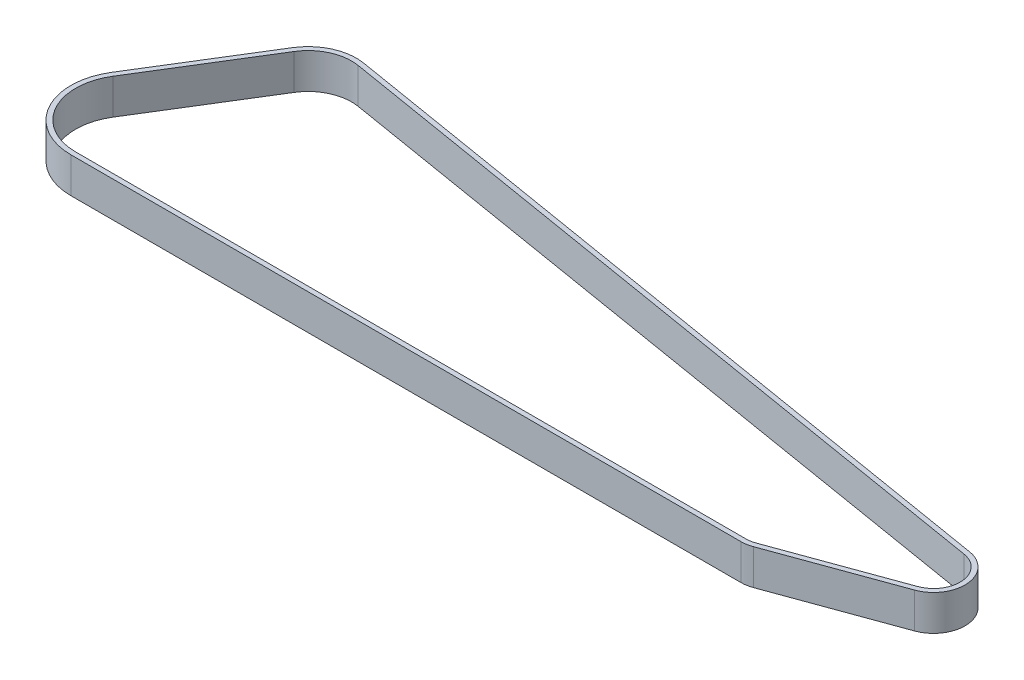
SolidWorks part; units mm, degrees
ref_plane "前视基准面" through (0, 0, 0) normal (0, 0, 1) x (1, 0, 0)
ref_plane "上视基准面" through (0, 0, 0) normal (0, 1, 0) x (1, 0, 0)
ref_plane "右视基准面" through (0, 0, 0) normal (1, 0, 0) x (0, 0, -1)
sketch "草图1" plane through (0, 0, 0) normal (0, 1, 0) x (1, 0, 0)
  line L1 (-17.5, -27.5) -> (17.5, -27.5)
  line L2 (-17.5, -27.5) -> (-17.5, 27.5)
  line L3 (-17.5, 27.5) -> (17.5, 27.5)
  line L4 (17.5, -27.5) -> (17.5, 27.5)
  line L5 (-17.5, -27.5) -> (17.5, 27.5) construction
  line L6 (-17.5, 27.5) -> (17.5, -27.5) construction
  point P0 (0, 0)
  dimension "D1" = 55
  dimension "D2" = 35
extrude "凸台-拉伸1" add sketch "草图1" along normal blind 1
sketch "草图2" plane through (0, 1, 0) normal (0, 1, 0) x (1, 0, 0)
  line L0 (-105.917, 0) -> (-62.25, 0) construction
  line L1 (106.75, 2.25) -> (121.75, 2.25)
  line L2 (-31.4474, 57.1013) -> (151.75, 26.6691)
  line L4 (124.0586, 2.6571) -> (154.0586, 13.5762)
  line L5 (-60.1618, 23.6059) -> (-42.6093, 52.0296)
  line L6 (121.75, 2.25) -> (121.75, 9) construction
  line L7 (121.75, -2.25) -> (121.75, -9) construction
  line L8 (-60.1618, -23.6059) -> (-42.6093, -52.0296)
  line L9 (124.0586, -2.6571) -> (154.0586, -13.5762)
  line L10 (121.75, -9) -> (128.5, -9)
  line L11 (-31.4474, -57.1013) -> (151.75, -26.6691)
  line L12 (106.75, -2.25) -> (121.75, -2.25)
  line L13 (-62.25, 16.25) -> (-62.25, -16.25)
  line L14 (106.75, 2.25) -> (106.75, -2.25)
  line L15 (106.75, 0) -> (124.0666, 0) construction
  arc A0 (-60.1618, 23.6059) -> (-62.25, 16.25) centre (-48.25, 16.25) ccw
  arc A1 (-31.4474, 57.1013) -> (-42.6093, 52.0296) centre (-33.25, 46.25) ccw
  arc A2 (121.75, 2.25) -> (124.0586, 2.6571) centre (121.75, 9) ccw
  arc A3 (154.0586, 13.5762) -> (151.75, 26.6691) centre (151.75, 19.9191) ccw
  arc A4 (154.0586, -13.5762) -> (151.75, -26.6691) centre (151.75, -19.9191) cw
  arc A5 (121.75, -2.25) -> (128.5, -9) centre (121.75, -9) cw
  arc A6 (-31.4474, -57.1013) -> (-42.6093, -52.0296) centre (-33.25, -46.25) cw
  arc A7 (-60.1618, -23.6059) -> (-62.25, -16.25) centre (-48.25, -16.25) cw
  line M10 (17.5, -27.5) -> (17.5, 27.5)
  line M11 (17.5, 27.5) -> (-17.5, 27.5)
  line M12 (-17.5, 27.5) -> (-17.5, -27.5)
  line M13 (-17.5, -27.5) -> (17.5, -27.5)
  dimension "D2" = 28
  dimension "D3" = 48.25
  dimension "D4" = 22
  dimension "D5" = 15
  dimension "D7" = 13.5
  dimension "D10" = 13.5
  dimension "D11" = 30
  dimension "D1" = 2.25
  dimension "D8" = 20
  dimension "D9" = 30
  dimension "D12" = 15
extrude "凸台-拉伸2" add sketch "草图2" along normal blind 3 contours A7 L8 A6 L11 A4 L9 A5 L12 L14 L1 A2 L4 A3 L2 A1 L5 A0 L13 | M13 M10 M11 M12 region at (37.3678, 1, 0) region at (0, 1, 0)
sketch "草图3" plane through (0, 4, 0) normal (0, 1, 0) x (1, 0, 0)
  circle A0 centre (-48.25, 16.25) radius 5
  circle A1 centre (-48.25, -16.25) radius 5
  circle A2 centre (-33.25, 46.25) radius 6.6982
  circle A3 centre (151.75, 19.9191) radius 2.5794
  circle A4 centre (121.75, 9) radius 2.5794
  circle A5 centre (121.75, -9) radius 2.5794
  circle A6 centre (151.75, -19.9191) radius 2.5794
  circle A7 centre (-33.25, -46.25) radius 6.6982
  dimension "D1" = 10
extrude "切除-拉伸1" cut sketch "草图3" against normal through all contours A0 | A1 region at (-48.25, 4, -16.25)
sketch "草图4" plane through (0, 4, 0) normal (0, 1, 0) x (1, 0, 0)
  circle A0 centre (-33.25, 46.25) radius 4
  circle A1 centre (-33.25, -46.25) radius 4
  dimension "D1" = 8
  dimension "D2" = 8
extrude "切除-拉伸2" cut sketch "草图4" against normal blind 2
sketch "草图5" plane through (0, 4, 0) normal (0, 1, 0) x (1, 0, 0)
  circle A0 centre (121.75, 9) radius 2
  circle A1 centre (121.75, -9) radius 2
  circle A2 centre (151.75, 19.9191) radius 2
  circle A3 centre (151.75, -19.9191) radius 2
  dimension "D1" = 4
extrude "切除-拉伸3" cut sketch "草图5" against normal blind 2
sketch "草图8" plane through (0, 1, 0) normal (0, -1, 0) x (1, 0, 0)
  line L1 (-39.75, -26.25) -> (-26.75, -26.25)
  line L2 (-39.75, -26.25) -> (-39.75, -66.25)
  line L3 (-39.75, -66.25) -> (-26.75, -66.25)
  line L4 (-26.75, -26.25) -> (-26.75, -66.25)
  line L5 (-39.75, -26.25) -> (-26.75, -66.25) construction
  line L6 (-39.75, -66.25) -> (-26.75, -26.25) construction
  line L16 (124.0586, 2.6571) -> (154.0586, 13.5762)
  line L17 (151.75, 26.6691) -> (-31.4474, 57.1013)
  line L18 (-42.6093, 52.0296) -> (-60.1618, 23.6059)
  line L19 (-62.25, 16.25) -> (-62.25, -16.25)
  line L20 (-60.1618, -23.6059) -> (-42.6093, -52.0296)
  line L21 (-31.4474, -57.1013) -> (151.75, -26.6691)
  line L22 (154.0586, -13.5762) -> (124.0586, -2.6571)
  line L23 (121.75, -2.25) -> (106.75, -2.25)
  line L24 (106.75, -2.25) -> (106.75, 2.25)
  line L25 (106.75, 2.25) -> (121.75, 2.25)
  line L26 (124.0586, 2.6571) -> (154.0586, 13.5762)
  line L27 (151.75, 26.6691) -> (-31.4474, 57.1013)
  line L28 (-42.6093, 52.0296) -> (-60.1618, 23.6059)
  line L31 (-31.4474, -57.1013) -> (151.75, -26.6691)
  line L32 (154.0586, -13.5762) -> (124.0586, -2.6571)
  line L33 (121.75, -2.25) -> (106.75, -2.25)
  line L34 (106.75, -2.25) -> (106.75, 2.25)
  line L35 (106.75, 2.25) -> (121.75, 2.25)
  arc A8 (154.0586, 13.5762) -> (151.75, 26.6691) centre (151.75, 19.9191) ccw
  arc A9 (-31.4474, 57.1013) -> (-42.6093, 52.0296) centre (-33.25, 46.25) ccw
  arc A10 (-60.1618, 23.6059) -> (-62.25, 16.25) centre (-48.25, 16.25) ccw
  arc A11 (-62.25, -16.25) -> (-60.1618, -23.6059) centre (-48.25, -16.25) ccw
  arc A12 (-42.6093, -52.0296) -> (-31.4474, -57.1013) centre (-33.25, -46.25) ccw
  arc A13 (151.75, -26.6691) -> (154.0586, -13.5762) centre (151.75, -19.9191) ccw
  arc A14 (124.0586, -2.6571) -> (121.75, -2.25) centre (121.75, -9) ccw
  arc A15 (121.75, 2.25) -> (124.0586, 2.6571) centre (121.75, 9) ccw
  arc A16 (154.0586, 13.5762) -> (151.75, 26.6691) centre (151.75, 19.9191) ccw
  arc A17 (-31.4474, 57.1013) -> (-42.6093, 52.0296) centre (-33.25, 46.25) ccw
  arc A18 (-60.1618, 23.6059) -> (-62.25, 16.25) centre (-48.25, 16.25) ccw
  arc A19 (-62.25, -16.25) -> (-60.1618, -23.6059) centre (-48.25, -16.25) ccw
  arc A20 (-42.6093, -52.0296) -> (-31.4474, -57.1013) centre (-33.25, -46.25) ccw
  arc A21 (151.75, -26.6691) -> (154.0586, -13.5762) centre (151.75, -19.9191) ccw
  arc A22 (124.0586, -2.6571) -> (121.75, -2.25) centre (121.75, -9) ccw
  arc A23 (121.75, 2.25) -> (124.0586, 2.6571) centre (121.75, 9) ccw
  point P0 (-33.25, -46.25)
  arc M32 (-42.6093, -52.0296) -> (-31.4474, -57.1013) centre (-33.25, -46.25) ccw
  line M33 (-31.4474, -57.1013) -> (151.75, -26.6691)
  dimension "D1" = 13
  dimension "D2" = 40
  dimension "D3" = 0
extrude "凸台-拉伸3" add sketch "草图8" along normal blind 7 contours L4 L1 L2 M32 M33 region at (-33.2258, 1, -41.4837)
mirror "镜向1" about plane through (0, 0, 0) normal (0, 0, 1) of "凸台-拉伸3"
sketch "草图9" plane through (0, -6, 0) normal (0, -1, 0) x (1, 0, 0)
  line L0 (-39.75, -26.25) -> (-26.75, -26.25) construction
  line L2 (-38.25, -53.75) -> (-38.25, -27.75)
  line L3 (-38.25, -27.75) -> (-28.25, -27.75)
  line L4 (-28.25, -53.75) -> (-28.25, -27.75)
  line L5 (-35.5448, -54.7408) -> (-28.25, -27.75) construction
  line L6 (-38.25, -27.75) -> (-31.223, -53.75) construction
  line L8 (-28.25, -53.75) -> (-38.25, -53.75)
  point P0 (-33.25, -46.25)
  dimension "D1" = 10
  dimension "D2" = 1.5
  dimension "D3" = 26
extrude "切除-拉伸4" cut sketch "草图9" against normal through all from offset 1.5 offset against normal yes
mirror "镜向2" about plane through (0, 0, 0) normal (0, 0, 1) of "切除-拉伸4"
sketch "草图10" plane through (0, 0, -53.75) normal (0, 0, 1) x (1, 0, 0)
  line L4 (-38.25, -4.5) -> (-28.25, -4.5)
  line L5 (-28.25, -4.5) -> (-28.25, 4)
  line L6 (-28.25, 4) -> (-38.25, 4)
  line L7 (-38.25, 4) -> (-38.25, -4.5)
  line L8 (-38.25, -4.5) -> (-28.25, -4.5)
  line L9 (-28.25, -4.5) -> (-28.25, 4)
  line L10 (-28.25, 4) -> (-38.25, 4)
  line L11 (-38.25, 4) -> (-38.25, -4.5)
  circle A0 centre (-33.25, -1.5) radius 1.5
  dimension "D2" = 3
  dimension "D3" = 3
  dimension "D1" = 0
extrude "切除-拉伸5" cut sketch "草图10" against normal through all contours A0 region at (-33.25, -1.5, -53.75)
mirror "镜向3" about plane through (0, 0, 0) normal (0, 0, 1) of "切除-拉伸5"
sketch "草图14" plane through (0, 4, 0) normal (0, 1, 0) x (1, 0, 0)
  line L0 (-31.4527, 57.1022) -> (152.8529, 26.5784)
  line L1 (154.0586, 13.5762) -> (124.0586, 2.6571)
  line L2 (-48.25, 2.25) -> (121.75, 2.25)
  line L3 (-60.1618, 23.6059) -> (-42.6093, 52.0296)
  line L4 (-31.2517, 58.3156) -> (153.0538, 27.7919)
  line L5 (154.4793, 12.4204) -> (124.4793, 1.5013)
  line L6 (-48.25, 1.02) -> (121.75, 1.02)
  line L7 (-61.2083, 24.2522) -> (-43.6558, 52.6759)
  arc A0 (-60.1618, 23.6059) -> (-48.25, 2.25) centre (-48.25, 16.25) ccw
  arc A1 (-31.4527, 57.1022) -> (-42.6093, 52.0296) centre (-33.25, 46.25) ccw
  arc A3 (121.75, 2.25) -> (124.0586, 2.6571) centre (121.75, 9) ccw
  arc A4 (154.0586, 13.5762) -> (152.8529, 26.5784) centre (151.75, 19.9191) ccw
  arc A5 (154.4793, 12.4204) -> (153.0538, 27.7919) centre (151.75, 19.9191) ccw
  arc A6 (121.75, 1.02) -> (124.4793, 1.5013) centre (121.75, 9) ccw
  arc A7 (-61.2083, 24.2522) -> (-48.25, 1.02) centre (-48.25, 16.25) ccw
  arc A8 (-31.2517, 58.3156) -> (-43.6558, 52.6759) centre (-33.25, 46.25) ccw
  dimension "D1" = 22
  dimension "D2" = 28
  dimension "D3" = 1.23
  dimension "D4" = 13.5
extrude "凸台-拉伸9" add sketch "草图14" along normal blind 10 from offset 1 offset against normal yes
sketch "草图15" plane through (0, 4, 0) normal (0, 1, 0) x (1, 0, 0)
  line L1 (-283.8143, 153.9565) -> (210.2461, 153.9565)
  line L2 (-283.8143, 153.9565) -> (-283.8143, -86.0981)
  line L3 (-283.8143, -86.0981) -> (210.2461, -86.0981)
  line L4 (210.2461, 153.9565) -> (210.2461, -86.0981)
  line L5 (-283.8143, 153.9565) -> (210.2461, -86.0981) construction
  line L6 (-283.8143, -86.0981) -> (210.2461, 153.9565) construction
  point P0 (-36.7841, 33.9292)
extrude "切除-拉伸6" cut sketch "草图15" against normal blind 10
